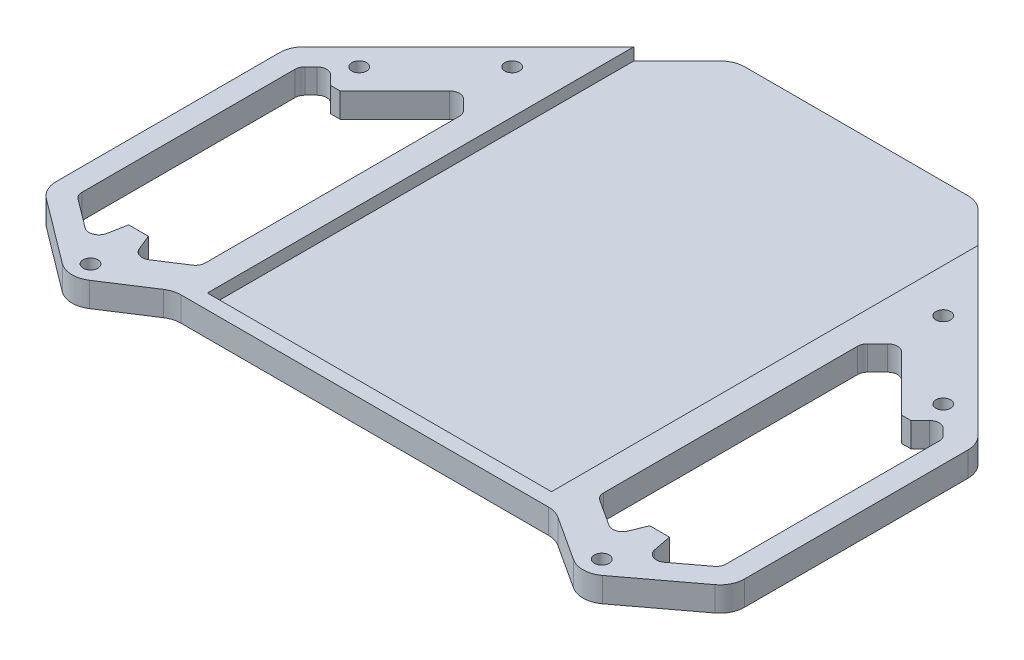
SolidWorks part; units mm, degrees
ref_plane "Front Plane" through (0, 0, 0) normal (0, 0, 1) x (1, 0, 0)
ref_plane "Top Plane" through (0, 0, 0) normal (0, 1, 0) x (1, 0, 0)
ref_plane "Right Plane" through (0, 0, 0) normal (1, 0, 0) x (0, 0, -1)
sketch "Sketch1" plane through (0, 0, 0) normal (0, 1, 0) x (1, 0, 0)
  line L0 (-52.1641, -38.6452) -> (-70, -25.2479)
  line L1 (-70, -25.2479) -> (-70, 24.7523)
  line L2 (-70, 24.7523) -> (-24.7523, 70)
  line L3 (-52.1641, -38.6452) -> (-38.8516, -30)
  line L4 (0, -30) -> (0, 70)
  line L5 (0, -30) -> (-38.8516, -30)
  line L6 (-59.397, 28.2843) -> (-43.8406, 43.8406) construction
  line L7 (-51.9976, -33.7676) -> (-63.9796, -15.3169) construction
  line L8 (-24.7523, 70) -> (0, 70)
  line L9 (0, 0) -> (-85, 0) construction
  line L10 (-43.8406, 43.8406) -> (0, 0) construction
  line L11 (-51.9976, -33.7676) -> (0, 0) construction
  line L12 (-59.0038, 22.1) -> (-57.096, 22.1)
  line L13 (-65.5, 22.1812) -> (-65.5, -23)
  line L14 (-55, -23) -> (-51, -23)
  line L15 (-40.5, 30.6005) -> (-40.5, -23)
  line L16 (-53, 22.1) -> (-53, -23) construction
  line L17 (-65.5, 22.1812) -> (-62.2925, 25.3887)
  line L18 (-62.2925, 25.3887) -> (-59.0038, 22.1)
  line L19 (-57.096, 22.1) -> (-44.5477, 34.6482)
  line L20 (-44.5477, 34.6482) -> (-40.5, 30.6005)
  line L21 (-65.5, -23) -> (-56.3366, -29.883)
  line L22 (-56.3366, -29.883) -> (-55, -23)
  line L23 (-51, -23) -> (-48.7962, -28.3876)
  line L24 (-48.7962, -28.3876) -> (-40.5, -23)
  circle A0 centre (0, 0) radius 85 construction
  circle A1 centre (-43.8406, 43.8406) radius 1.5
  circle A2 centre (-51.9976, -33.7676) radius 1.5
  circle A3 centre (-59.397, 28.2843) radius 1.5
  circle A4 centre (-63.9796, -15.3169) radius 1.5 construction
  dimension "D7" = 3
  dimension "D17" = 170
  dimension "D20" = 12.5
  dimension "D2" = 30
  dimension "D3" = 4
  dimension "D4" = 4
  dimension "D5" = 4.5
  dimension "D6" = 70
  dimension "D8" = 62
  dimension "D9" = 22
  dimension "D10" = 22
  dimension "D11" = 25
  dimension "D12" = 45.1
  dimension "D13" = 53
  dimension "D14" = 45
  dimension "D15" = 33
  dimension "D16" = 23
  dimension "D18" = 5
  dimension "D19" = 70
  dimension "D21" = 5
  dimension "D22" = 5
  dimension "D23" = 4
  dimension "D24" = 6
  dimension "D25" = 15
extrude "Boss-Extrude1" add sketch "Sketch1" along normal blind 5
fillet "Fillet1" radius 2 8 edges at (-40.5, 2.5, 23) (-48.7962, 2.5, 28.3876) (-56.3366, 2.5, 29.883) (-65.5, 2.5, 23) (-65.5, 2.5, -22.1812) (-62.2925, 2.5, -25.3887) (-40.5, 2.5, -30.6005) (-44.5477, 2.5, -34.6482)
mirror "Mirror1" about plane through (0, 5, 30) normal (-1, 0, 0) of "Fillet1", "Boss-Extrude1"
sketch "Sketch2" plane through (0, 5, 0) normal (0, 1, 0) x (1, 0, 0)
  line L0 (24.7523, 70) -> (-24.7523, 70) construction
  line L1 (-35, 70) -> (35, 70)
  line L2 (-35, 70) -> (-35, -27)
  line L3 (-35, -27) -> (35, -27)
  line L4 (35, 70) -> (35, -27)
  line L5 (-38.8516, -30) -> (38.8516, -30) construction
  dimension "D1" = 3
  dimension "D2" = 70
  dimension "D3" = 35
extrude "Cut-Extrude1" cut sketch "Sketch2" against normal blind 2.5
fillet "Fillet2" radius 5 10 edges at (70, 2.5, -24.7523) (24.7523, 1.25, -70) (-24.7523, 1.25, -70) (-70, 2.5, -24.7523) (-70, 2.5, 25.2479) (70, 2.5, 25.2479) (52.1641, 2.5, 38.6452) (38.8516, 2.5, 30) (-38.8516, 2.5, 30) (-52.1641, 2.5, 38.6452)
